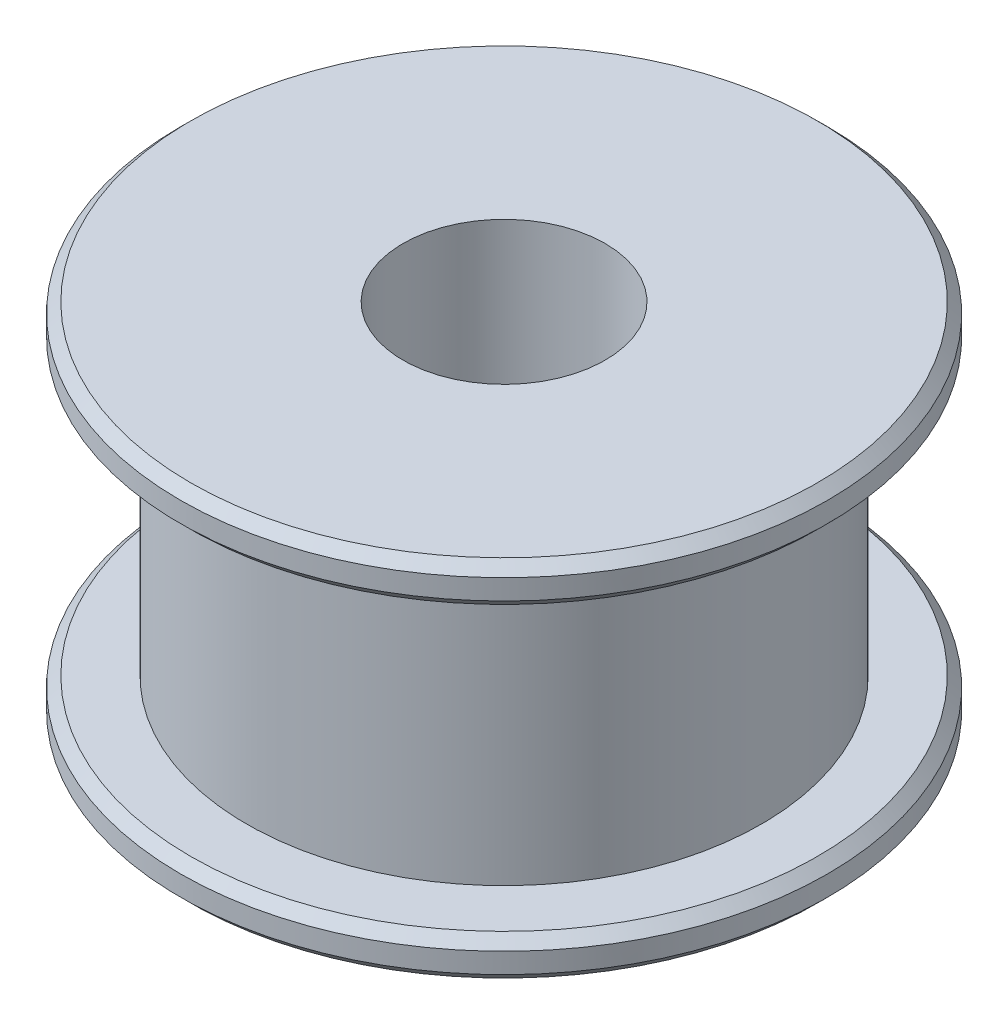
SolidWorks part; units mm, degrees
ref_plane "Front Plane" through (0, 0, 0) normal (0, 0, 1) x (1, 0, 0)
ref_plane "Top Plane" through (0, 0, 0) normal (0, 1, 0) x (1, 0, 0)
ref_plane "Right Plane" through (0, 0, 0) normal (1, 0, 0) x (0, 0, -1)
sketch "Sketch4" plane through (0, 0, 0) normal (0, 0, 1) x (1, 0, 0)
  line L0 (0, 0) -> (0, 9) construction
  line L1 (2.5, 0) -> (8, 0)
  line L2 (8, 0) -> (8, 1)
  line L3 (8, 1) -> (6.3662, 1)
  line L4 (6.3662, 1) -> (6.3662, 8)
  line L5 (6.3662, 8) -> (8, 8)
  line L6 (8, 8) -> (8, 9)
  line L7 (8, 9) -> (2.5, 9)
  line L8 (2.5, 9) -> (2.5, 0)
  dimension "D2" = 12.7324
  dimension "D3" = 7
  dimension "D4" = 9
  dimension "D5" = 16
  dimension "D6" = 1
revolve "Revolve2" add sketch "Sketch4" angle 360 about L0
chamfer "Chamfer1" distance 0.25 angle 45 4 edges at (0, 0, -8) (0, 1, -8) (0, 8, -8) (0, 9, -8)
equation "\"D2@Sketch4\" = 40/pi"
